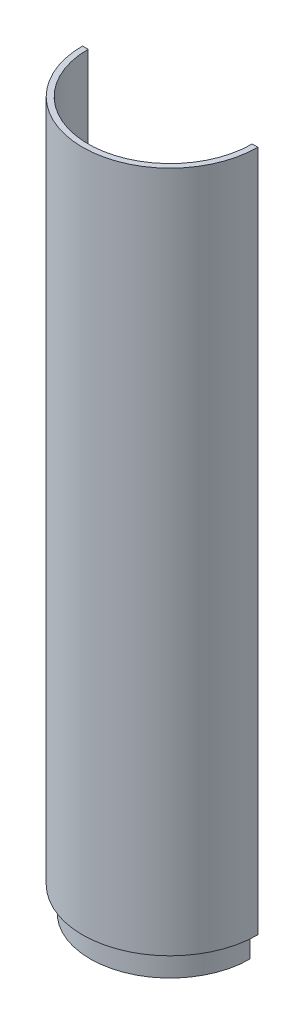
SolidWorks part; units mm, degrees
ref_plane "Front Plane" through (0, 0, 0) normal (0, 0, 1) x (1, 0, 0)
ref_plane "Top Plane" through (0, 0, 0) normal (0, 1, 0) x (1, 0, 0)
ref_plane "Right Plane" through (0, 0, 0) normal (1, 0, 0) x (0, 0, -1)
sketch "Sketch1" plane through (0, 0, 0) normal (0, 1, 0) x (1, 0, 0)
  circle A0 centre (0, 0) radius 49.4538
  dimension "D1" = 98.9076
extrude "Boss-Extrude1" add sketch "Sketch1" along normal blind 3.81 and the other way blind 6.35
sketch "Sketch2" plane through (0, 3.81, 0) normal (0, 1, 0) x (1, 0, 0)
  circle A0 centre (0, 0) radius 49.4538
  dimension "D1" = 98.9076
extrude "Boss-Extrude2" add sketch "Sketch2" along normal blind 381
shell "Shell1" thickness 3.175 removed face at (0, 384.81, 49.4538)
sketch "Sketch4" plane through (0, -6.35, 0) normal (0, -1, 0) x (1, 0, 0)
  line L0 (49.4538, 0) -> (12.7, 0)
  line L1 (-12.7, 0) -> (-49.4538, 0)
  circle A0 centre (0, 0) radius 49.4538 construction
  arc A1 (-12.7, 0) -> (12.7, 0) centre (0, 0) ccw
  arc A2 (-49.4538, 0) -> (49.4538, 0) centre (0, 0) ccw
  dimension "D1" = 25.4
extrude "Cut-Extrude1" cut sketch "Sketch4" against normal through all contours A2 L0 A1 L1
sketch "Sketch5" plane through (0, -3.175, 0) normal (0, 1, 0) x (1, 0, 0)
  line L0 (-46.2788, 0) -> (-12.7, 0)
  line L1 (12.7, 0) -> (46.2788, 0)
  arc A0 (-46.2788, 0) -> (46.2788, 0) centre (0, 0) ccw
  arc A1 (12.7, 0) -> (-12.7, 0) centre (0, 0) ccw
  dimension "D1" = 25.4
extrude "Boss-Extrude3" add sketch "Sketch5" along normal blind 3.81
sketch "Sketch7" plane through (0, -6.35, 0) normal (0, -1, 0) x (1, 0, 0)
  circle A0 centre (0, 0) radius 49.4538
  circle A1 centre (0, 0) radius 45.085
  dimension "D1" = 98.9076
  dimension "D2" = 90.17
extrude "Cut-Extrude2" cut sketch "Sketch7" against normal blind 6.35
sketch "Sketch9" plane through (0, -6.35, 0) normal (0, -1, 0) x (1, 0, 0)
  line L0 (45.085, 0) -> (12.7, 0)
  line L1 (-12.7, 0) -> (-45.085, 0)
  arc A0 (45.085, 0) -> (-45.085, 0) centre (0, 0) ccw
  arc A1 (-12.7, 0) -> (12.7, 0) centre (0, 0) ccw
  dimension "D2" = 25.4
extrude "Boss-Extrude4" add sketch "Sketch9" along normal blind 7.62 contours A0 L1 A1 L0
sketch "Sketch10" plane through (0, 0.635, 0) normal (0, 1, 0) x (1, 0, 0)
  circle A2 centre (0, 0) radius 16.51
  circle A3 centre (0, 0) radius 35.56
  dimension "D1" = 33.02
  dimension "D2" = 71.12
extrude "Cut-Extrude3" cut sketch "Sketch10" against normal blind 6.35 contours A3
sketch "Sketch11" plane through (0, -5.715, 0) normal (0, 1, 0) x (1, 0, 0)
  circle A0 centre (0, 0) radius 8.382
  dimension "D1" = 16.764
extrude "Cut-Extrude4" cut sketch "Sketch11" against normal blind 5.08
sketch "Sketch12" plane through (0, -10.795, 0) normal (0, 1, 0) x (1, 0, 0)
  circle A0 centre (0, 0) radius 3.302
  dimension "D1" = 6.604
extrude "Cut-Extrude5" cut sketch "Sketch12" against normal through all
sketch "Sketch13" plane through (0, 0.635, 0) normal (0, 1, 0) x (1, 0, 0)
  line L0 (-46.2788, 0) -> (-35.56, 0)
  line L1 (35.56, 0) -> (46.2788, 0)
  arc A0 (-46.2788, 0) -> (46.2788, 0) centre (0, 0) ccw
  arc A1 (-35.56, 0) -> (35.56, 0) centre (0, 0) ccw
extrude "Boss-Extrude5" add sketch "Sketch13" along normal blind 5.08
sketch "Sketch14" plane through (0, -13.97, 0) normal (0, -1, 0) x (1, 0, 0)
  circle A0 centre (0, 15.24) radius 4.191
  dimension "D1" = 8.382
  dimension "D2" = 15.24
extrude "Cut-Extrude6" cut sketch "Sketch14" against normal through all
